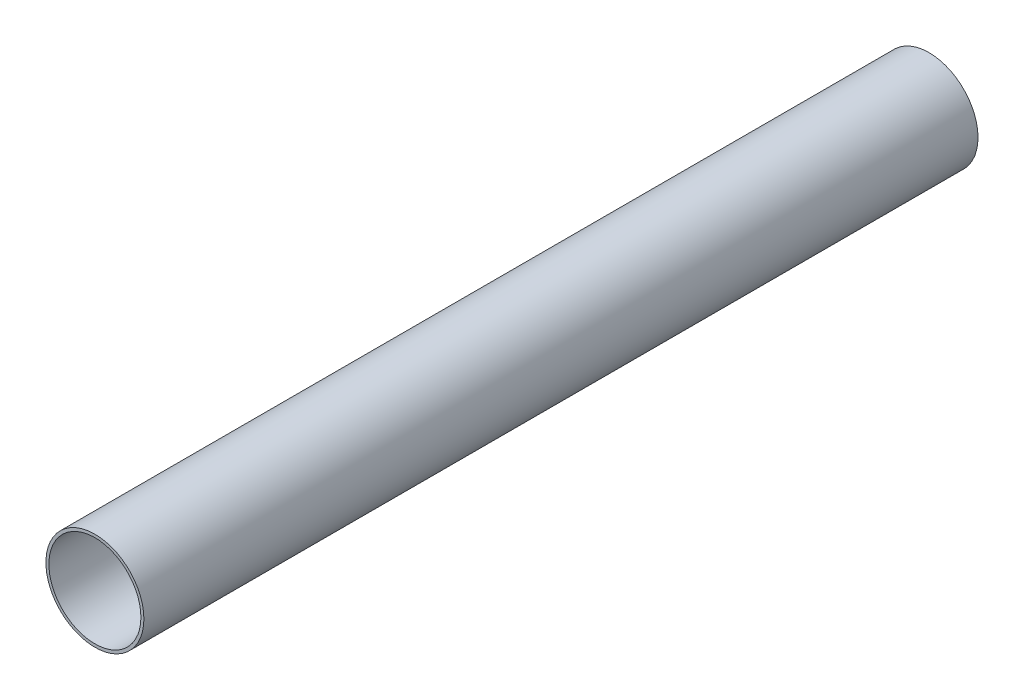
SolidWorks part; units mm, degrees
ref_plane "Front Plane" through (0, 0, 0) normal (0, 0, 1) x (1, 0, 0)
ref_plane "Top Plane" through (0, 0, 0) normal (0, 1, 0) x (1, 0, 0)
ref_plane "Right Plane" through (0, 0, 0) normal (1, 0, 0) x (0, 0, -1)
sketch "Sketch1" plane through (0, 0, 0) normal (0, 0, 1) x (1, 0, 0)
  circle A0 centre (0, 0) radius 20.555
  circle A1 centre (0, 0) radius 19.305
  dimension "D1" = 41.11
  dimension "D2" = 38.61
extrude "Boss-Extrude3" add sketch "Sketch1" against normal blind 350
